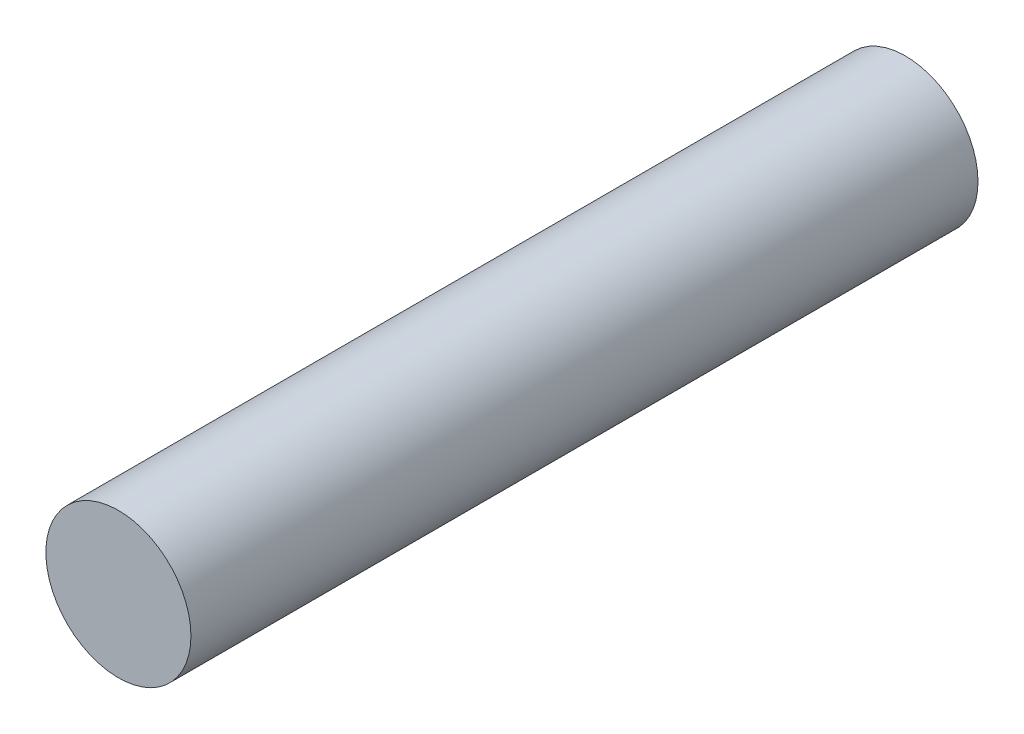
SolidWorks part; units mm, degrees
ref_plane "Front Plane" through (0, 0, 0) normal (1, 0, 0) x (0, 1, 0)
ref_plane "Top Plane" through (0, 0, 0) normal (0, 0, 1) x (0, 1, 0)
ref_plane "Right Plane" through (0, 0, 0) normal (0, 1, 0) x (-1, 0, 0)
sketch "Sketch1" plane through (0, 0, 0) normal (0, 0, 1) x (0, 1, 0)
  circle A0 centre (0, 0) radius 10
  dimension "D1" = 20
extrude "Boss-Extrude1" add sketch "Sketch1" along normal blind 23.5 and the other way blind 23.5
sketch "Sketch3" plane through (0, 0, 23.5) normal (0, 0, 1) x (1, 0, 0)
  circle A0 centre (0, 0) radius 10 construction
  circle A1 centre (0, 0) radius 10
sketch "Sketch5" plane through (0, 0, 0) normal (0, 0, 1) x (0, 1, 0)
  line L1 (-2.5, 11.5) -> (2.5, 11.5)
  line L2 (-2.5, 11.5) -> (-2.5, 8.5)
  line L3 (-2.5, 8.5) -> (2.5, 8.5)
  line L4 (2.5, 11.5) -> (2.5, 8.5)
  line L5 (-2.5, 11.5) -> (2.5, 8.5) construction
  line L6 (-2.5, 8.5) -> (2.5, 11.5) construction
  circle A0 centre (0, 0) radius 10 construction
  point P0 (0, 10)
  dimension "D1" = 5
  dimension "D2" = 3
extrude "Boss-Extrude3" add sketch "Sketch5" along normal blind 11.5 and the other way blind 11.5
fillet "Fillet1" radius 1.5 6 edges at (-10.5912, -2.5, -11.5) (-10.5912, 2.5, -11.5) (-11.5, 0, -11.5) (-10.5912, -2.5, 11.5) (-10.5912, 2.5, 11.5) (-11.5, 0, 11.5)
sketch "Sketch6" plane through (0, 0, 23.5) normal (0, 0, 1) x (1, 0, 0)
  circle A0 centre (0, 0) radius 10
extrude "Boss-Extrude4" add sketch "Sketch6" along normal blind 61.5
sketch "Sketch7" plane through (0, 0, 85) normal (0, 0, 1) x (1, 0, 0)
  line L1 (-9.6825, 2.5) -> (-11.5, 2.5)
  line L3 (-9.6825, -2.5) -> (-11.5, -2.5)
  line L4 (-11.5, 2.5) -> (-11.5, -2.5)
  arc A0 (-9.6825, 2.5) -> (-9.6825, -2.5) centre (0, 0) ccw
  point P3 (-10, 0)
extrude "Boss-Extrude5" add sketch "Sketch7" against normal blind 50
sketch "Sketch8" plane through (0, 0, 85) normal (0, 0, 1) x (1, 0, 0)
  line L1 (-9.6825, 2.5) -> (-11.5, 2.5)
  line L3 (-9.6825, -2.5) -> (-11.5, -2.5)
  line L4 (-11.5, 2.5) -> (-11.5, -2.5)
  arc A0 (-9.6825, 2.5) -> (-9.6825, -2.5) centre (0, 0) ccw
  point P3 (-10, 0)
extrude "Cut-Extrude1" cut sketch "Sketch8" against normal blind 15
fillet "Fillet2" radius 1.5 6 edges at (-10.5912, -2.5, 70) (-11.5, 0, 70) (-10.5912, 2.5, 70) (-10.5912, -2.5, 35) (-10.5912, 2.5, 35) (-11.5, 0, 35)
